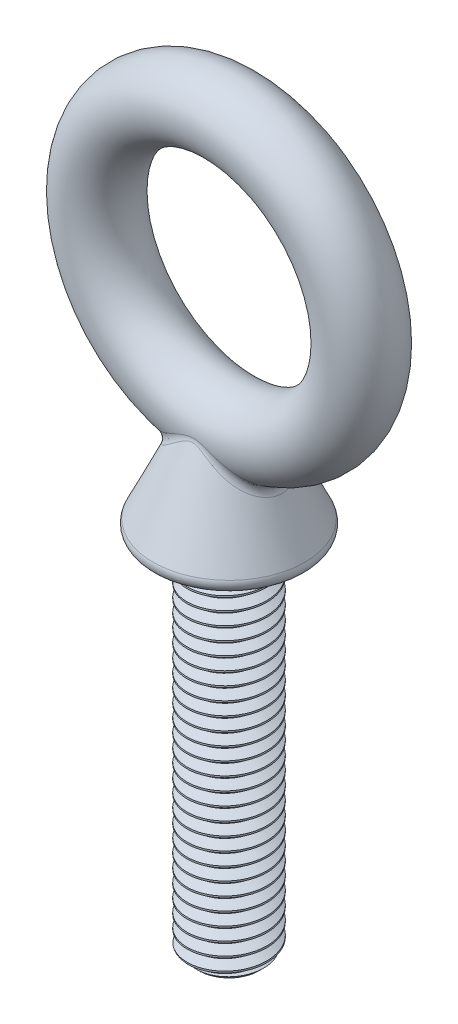
SolidWorks part; units mm, degrees
note: '?' marks a value the reader was unsure of.
ref_plane "Front Plane" through (0, 0, 0) normal (0, 0, 1) x (1, 0, 0)
ref_plane "Top Plane" through (0, 0, 0) normal (0, 1, 0) x (1, 0, 0)
ref_plane "Right Plane" through (0, 0, 0) normal (1, 0, 0) x (0, 0, -1)
sketch "Sketch1" plane through (0, 0, 0) normal (0, 0, 1) x (1, 0, 0)
  line L0 (0, -23.4156) -> (0, -82.9469) construction
  line L1 (-5.5562, -82.9469) -> (5.5563, -82.9469) construction
  line L2 (5.7527, -82.8335) -> (5.7527, -84.6478) construction
  line L3 (0, -23.4156) -> (0, -13.4937) construction
  line L4 (-10.7156, -32.1469) -> (10.7156, -32.1469) construction
  line L5 (5.7527, -84.6478) -> (4.1814, -83.7406) construction
  line L6 (4.1814, -83.7406) -> (5.7527, -82.8335) construction
  line L7 (4.1814, -83.7406) -> (4.3778, -83.7406) construction
  line L8 (5.7527, -83.7406) -> (5.5563, -83.7406) construction
  line L9 (4.3778, -83.854) -> (4.3778, -83.6272) construction
  line L10 (5.5563, -84.5344) -> (5.5563, -82.9469) construction
  line L11 (5.6545, -84.5911) -> (5.6545, -82.8902) construction
  circle A0 centre (0, 0) radius 23.4156 construction
  circle A1 centre (0, 18.4547) radius 4.9609 construction
  circle A2 centre (0, 0) radius 13.4938 construction
  point P7 (0, -23.4156)
  point P9 (0, -32.1469)
  point P10 (0, 23.4156)
  point P11 (0, 13.4937)
  point P14 (0, -82.9469)
  point P17 (0, 0)
  point P19 (0, -18.4547)
  point P21 (0, -32.1469)
  point P32 (4.3778, -83.7406)
  point P35 (5.5563, -83.7406)
  point P38 (5.6545, -83.7406)
  dimension "Pitch" = 1.8143
  dimension "D1" = 0.2268
sketch "Sketch2" plane through (0, 0, 0) normal (0, 1, 0) x (1, 0, 0)
  circle A0 centre (0, 0) radius 5.5563
extrude "Boss-Extrude1" add sketch "Sketch2" against normal up to vertex (82.9469 mm away) from vertex at -32.1469 starting at point (0, -32.1469, 0)
sketch "Sketch3" plane through (0, -82.9469, 0) normal (0, -1, 0) x (1, 0, 0)
  circle A1 centre (0, 0) radius 5.5563
  circle A2 centre (0, 0) radius 5.5563
  point P0 (5.5563, 0)
  point P1 (0, -5.5563)
  dimension "D1" = 0
sketch "Sketch4" plane through (0, 0, 0) normal (0, 0, 1) x (1, 0, 0)
  line L0 (4.3778, -83.6272) -> (4.3778, -83.854)
  line L1 (4.3778, -83.854) -> (5.6545, -84.5911)
  line L2 (5.6545, -84.5911) -> (5.6545, -82.8902)
  line L3 (5.6545, -82.8902) -> (4.3778, -83.6272)
sketch "Sketch5" plane through (0, -82.9469, 0) normal (0, -1, 0) x (1, 0, 0)
  circle A0 centre (0, 0) radius 4.1814
extrude "Cut-Extrude1" cut sketch "Sketch5" against normal through all draft 45 flip side to cut
sketch "Sketch6" plane through (0, 0, 0) normal (1, 0, 0) x (0, 0, -1)
  circle A0 centre (0, 18.4547) radius 4.9609
ref_axis "Axis1" through (0, 0, -7.6398) along (0, 0, 1)
revolve "Revolve1" add sketch "Sketch6" angle 360 about axis through (0, 0, -7.6398) along (0, 0, 1)
sketch "Sketch8" plane through (0, 0, 0) normal (0, 0, 1) x (1, 0, 0)
  line L0 (0, -32.1469) -> (0, -18.4547)
  line L1 (0, -18.4547) -> (-4.9609, -18.4547)
  line L2 (-9.4754, -32.1469) -> (-10.7156, -32.1469) construction
  line L3 (-10.7156, -32.1469) -> (-10.7156, -30.9066) construction
  line L4 (0, -32.1469) -> (10.7156, -32.1469) construction
  line L5 (-10.7156, -32.1469) -> (10.7156, -32.1469) construction
  line L6 (-10.5967, -30.3766) -> (-4.9609, -18.4547)
  line L7 (-10.7156, -32.1469) -> (0, -32.1469) construction
  line L9 (-9.4754, -32.1469) -> (0, -32.1469)
  arc A0 (-10.5967, -30.3766) -> (-9.4754, -32.1469) centre (-9.4754, -30.9066) ccw
  circle A1 centre (0, -18.4547) radius 4.9609 construction
  dimension "D1" = 1.2402
revolve "Revolve2" add sketch "Sketch8" angle 360 about L0
fillet "Fillet1" radius 1.2402 1 edges at (5.3556, -21.3947, 3.4131)
sketch "SketchX" plane through (0, 0, 0) normal (1, 0, 0) x (0, 0, -1)
  line L0 (5.5562, -82.9469) -> (5.5562, -78.4112) construction
  line L1 (0, -82.9469) -> (5.5562, -82.9469) construction
  dimension "D1" = 4.5357
  dimension "D2" = 5.5562
ref_axis "Center Axis 1" through (0, 21.5506, 0) along (0, -1, 0)?
ref_axis "Center Axis 2" through (0, 0, -7.6398) along (0, 0, 1)?
curve "Helix/Spiral1" pitch 1.8143 height 52.6143 turns 29 parameters "Pitch"=1.8143
ref_plane "Plane1" through (0, -32.1469, 0) normal (0, -1, 0) x (1, 0, 0)
split "Split1" trim tools "Plane1" bodies to split 109 resulting bodies 110 111
sweep "Cut-Sweep1" cut profiles "Sketch4" path "Helix/Spiral1"
sketch "Sketch9" plane through (0, -32.1469, 0) normal (0, -1, 0) x (1, 0, 0)
  line L0 (-10.7156, 0) -> (10.7156, 0) construction
  circle A0 centre (0, 0) radius 5.5562
extrude "Boss-Extrude2" add sketch "Sketch9" along normal blind 2.54 draft 45
equation "\"D3@Helix/Spiral1\" = \"Pitch@Helix/Spiral1\" + \"Thread Lg.@Sketch1\""
equation "\"D1@Sketch8\" = \"A@Sketch1\" / 8"
equation "\"D1@Fillet1\" = \"A@Sketch1\" / 8"
equation "\"D1@SketchX\"= \"Pitch@Helix/Spiral1\"*2.5"
equation "\"D1@Sketch1\"=\"Pitch@Sketch1\"/8"
equation "\"Pitch@Helix/Spiral1\"=\"Pitch@Sketch1\""
equation "\"D2@SketchX\" = \"Thread OD@Sketch1\" / 2"
